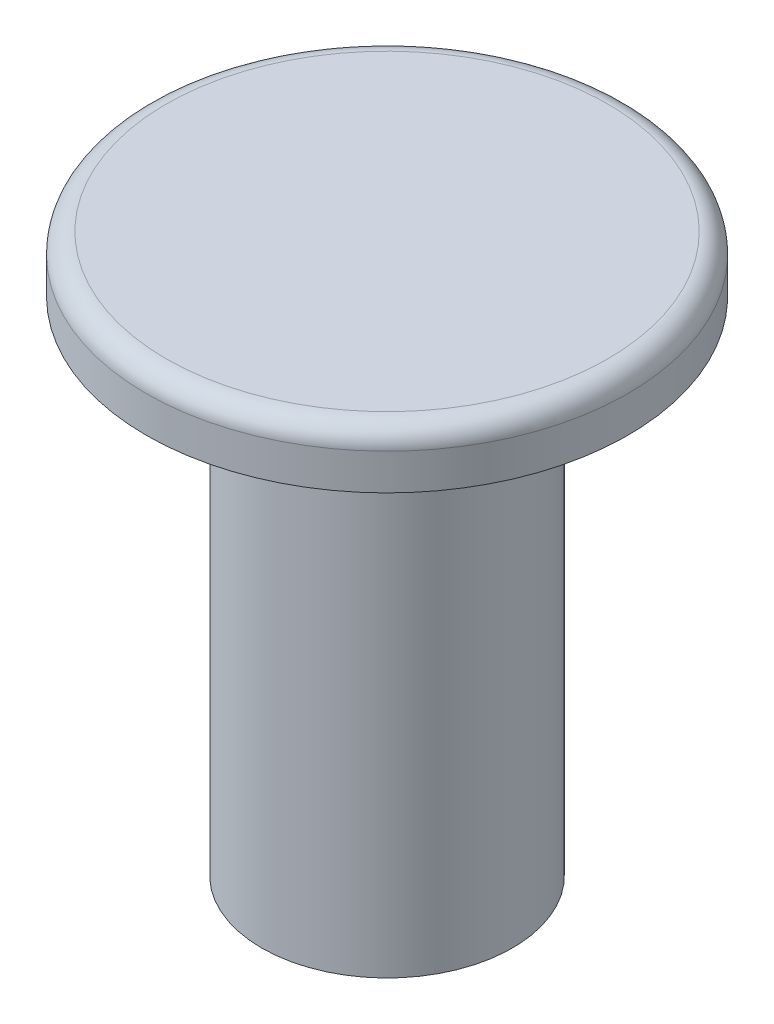
SolidWorks part; units mm, degrees
material "Brass"
ref_plane "Front Plane" through (0, 0, 0) normal (0, 0, 1) x (1, 0, 0)
ref_plane "Top Plane" through (0, 0, 0) normal (0, 1, 0) x (1, 0, 0)
ref_plane "Right Plane" through (0, 0, 0) normal (1, 0, 0) x (0, 0, -1)
sketch "Sketch1" plane through (0, 0, 0) normal (0, 1, 0) x (1, 0, 0)
  circle A0 centre (0, 0) radius 2.5
  dimension "D1" = 5
extrude "Boss-Extrude1" add sketch "Sketch1" along normal blind 10
sketch "Sketch2" plane through (0, 10, 0) normal (0, 1, 0) x (1, 0, 0)
  circle A0 centre (0, 0) radius 4.8
extrude "Boss-Extrude2" add sketch "Sketch2" along normal blind 1.12
fillet "Fillet2" radius 0.4 1 edges at (0, 11.12, 4.8)
ref_axis "Axis1" through (0, 13.6551, 0) along (0, -1, 0)
